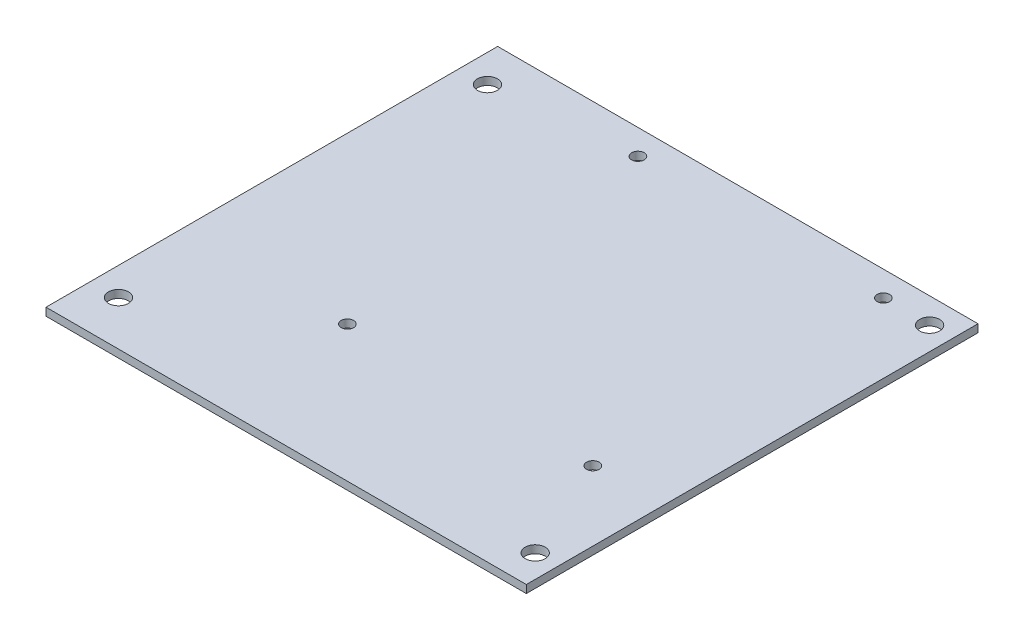
SolidWorks part; units mm, degrees
other "DetailItem3"
material "ABS"
ref_plane "Front Plane" through (0, 0, 0) normal (0, 0, 1) x (1, 0, 0)
ref_plane "Top Plane" through (0, 0, 0) normal (0, 1, 0) x (1, 0, 0)
ref_plane "Right Plane" through (0, 0, 0) normal (1, 0, 0) x (0, 0, -1)
sketch "Sketch1" plane through (0, 0, 0) normal (0, 1, 0) x (1, 0, 0)
  line L1 (-32.2441, 108.719) -> (64.6459, 108.719)
  line L2 (-32.2441, 108.719) -> (-32.2441, 18.549)
  line L3 (-32.2441, 18.549) -> (64.6459, 18.549)
  line L4 (64.6459, 108.719) -> (64.6459, 18.549)
  dimension "D1" = 96.89
  dimension "D2" = 90.17
extrude "PCB" add sketch "Sketch1" along normal blind 1.57
sketch "Sketch2" plane through (0, 1.57, 0) normal (0, 1, 0) x (1, 0, 0)
  line L0 (64.6459, 18.549) -> (64.6459, 108.719) construction
  line L1 (-32.2441, 18.549) -> (64.6459, 18.549) construction
  circle A0 centre (59.5659, 24.899) radius 2
  circle A1 centre (-26.1641, 27.439) radius 2
  circle A2 centre (-26.1641, 101.099) radius 2
  circle A3 centre (59.5659, 103.639) radius 2
  dimension "D3" = 4
  dimension "D6" = 4
  dimension "D11" = 4
  dimension "D12" = 4
  dimension "D1" = 5.08
  dimension "D2" = 6.35
  dimension "D4" = 90.81
  dimension "D5" = 8.89
  dimension "D7" = 90.81
  dimension "D8" = 5.08
  dimension "D9" = 85.09
  dimension "D10" = 82.55
extrude "M3 Mounting Holes" cut sketch "Sketch2" against normal blind 1.57
sketch "Sketch5" plane through (0, 1.57, 0) normal (0, 1, 0) x (1, 0, 0)
  line L0 (64.6459, 108.719) -> (-32.2441, 108.719) construction
  line L1 (-32.2441, 18.549) -> (-31.7441, 18.549)
  line L2 (-32.2441, 18.549) -> (-32.2441, 108.719)
  line L3 (-32.2441, 108.719) -> (-31.7441, 108.719)
  line L4 (-31.7441, 18.549) -> (-31.7441, 108.719)
  line L5 (-32.2441, 18.549) -> (64.6459, 18.549) construction
  line L6 (64.6459, 108.719) -> (64.1459, 108.719)
  line L7 (64.6459, 108.719) -> (64.6459, 18.549)
  line L8 (64.6459, 18.549) -> (64.1459, 18.549)
  line L9 (64.1459, 108.719) -> (64.1459, 18.549)
  dimension "D1" = 0.5
  dimension "D2" = 0.5
extrude "Cut-Extrude1" cut sketch "Sketch5" against normal through all
sketch "Sketch8" plane through (0, 1.57, 0) normal (0, 1, 0) x (1, 0, 0)
  line L1 (-31.7441, 18.549) -> (-31.7441, 108.719) construction
  line L3 (64.1459, 108.719) -> (-31.7441, 108.719) construction
  circle A0 centre (1.2559, 45.719) radius 1.25
  circle A1 centre (50.2559, 45.719) radius 1.25
  circle A2 centre (1.2559, 103.719) radius 1.25
  circle A3 centre (50.2559, 103.719) radius 1.25
  dimension "D1" = 2.5
  dimension "D3" = 2.5
  dimension "D5" = 2.5
  dimension "D6" = 2.5
  dimension "D2" = 5
  dimension "D4" = 63
  dimension "D7" = 58
  dimension "D8" = 58
  dimension "D9" = 49
  dimension "D10" = 33
  dimension "D11" = 33
  dimension "D12" = 49
extrude "RPi mounting hole" cut sketch "Sketch8" against normal blind 10
